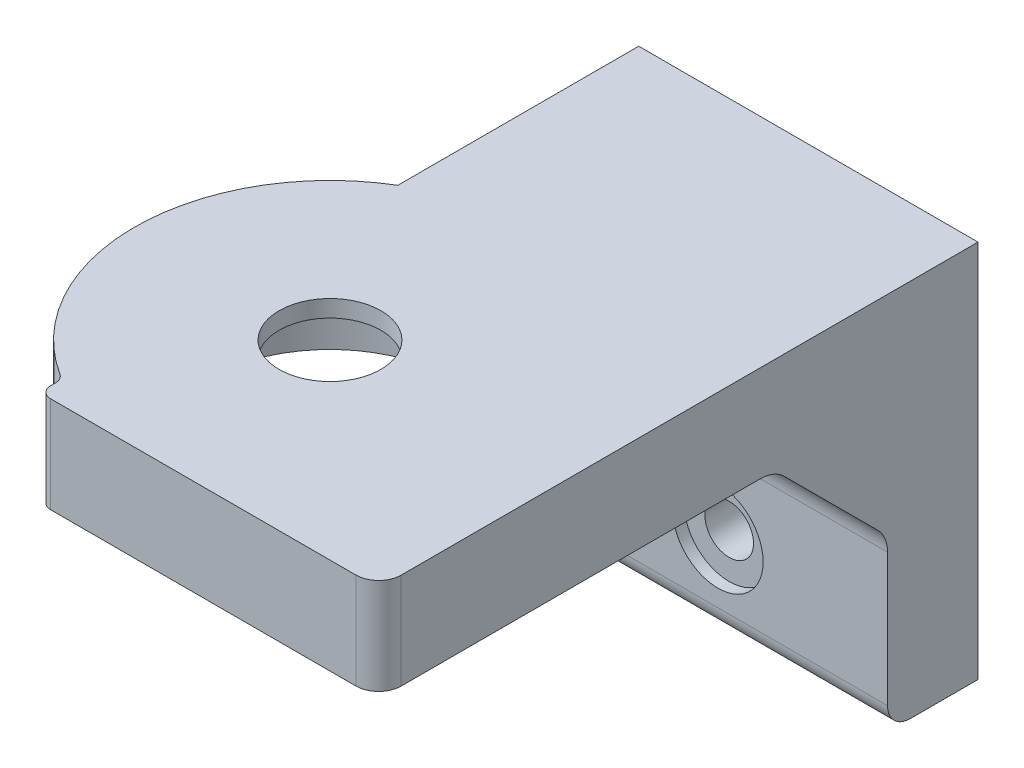
SolidWorks part; units mm, degrees
ref_plane "Front Plane" through (0, 0, 0) normal (0, 0, 1) x (1, 0, 0)
ref_plane "Top Plane" through (0, 0, 0) normal (0, 1, 0) x (1, 0, 0)
ref_plane "Right Plane" through (0, 0, 0) normal (1, 0, 0) x (0, 0, -1)
sketch "Croquis3" plane through (0, -625, 0) normal (0, 1, 0) x (1, 0, 0)
  line L0 (-40.3, 0) -> (-10.3, 0)
  line L1 (0, 0) -> (-20.6, 0) construction
  line L2 (-10.3, 0) -> (-10.3, -53)
  line L3 (-10.3, -270) -> (-10.3, 0) construction
  line L4 (-10.3, -53) -> (-40.3, -53)
  line L5 (-40.3, -53) -> (-40.3, -51)
  line L6 (-40.3, 0) -> (-40.3, -21.3)
  arc A0 (-40.3, -51) -> (-40.3, -21.3) centre (-31.45, -36.15) cw
  circle A1 centre (-31.45, -36.15) radius 11 construction
  circle A2 centre (-31.45, -36.15) radius 11
  circle A5 centre (-31.45, -36.15) radius 4.5
  circle A6 centre (-31.45, -36.15) radius 4.5
  dimension "D1" = 2
  dimension "D2" = 53
  dimension "D3" = 0.5
extrude "Saliente-Extruir2" add sketch "Croquis3" against normal blind 1.5 contours A0 L5 L4 L2 L0 L6 A2 | A2 A6 region at (-25.9749, -625, 25.0897) region at (-42.1389, -625, 36.15)
extrude "Saliente-Extruir3" add sketch "Croquis3<3>" against normal blind 7 from surface contours A0 L5 L4 L2 L0 L6 A2 region at (-25.9749, -625, 25.0897) starting at face at (-31.7062, -626.5, 29.7167)
sketch "Croquis3<3>" plane through (0, -625, 0) normal (0, 1, 0) x (1, 0, 0) same geometry as "Croquis3"
sketch "Croquis4" plane through (0, 0, 0) normal (0, 0, -1) x (-1, 0, 0)
  line L0 (10.3, -633.5) -> (10.3, -625) construction
  line L1 (40.3, -633.5) -> (10.3, -633.5)
  line L2 (40.3, -633.5) -> (40.3, -658.5)
  line L3 (40.3, -658.5) -> (10.3, -658.5)
  line L4 (10.3, -633.5) -> (10.3, -658.5)
  dimension "D1" = 25
extrude "Saliente-Extruir4" add sketch "Croquis4" against normal blind 8
chamfer "Chaflán1" distance 10 1 edges at (-25.3, -633.5, 8)
sketch "Croquis5" plane through (0, 0, 8) normal (0, 0, 1) x (1, 0, 0)
  line L0 (-40.3, -651) -> (-10.3, -651) construction
  line L1 (-40.3, -658.5) -> (-40.3, -643.5) construction
  line L2 (-10.3, -643.5) -> (-10.3, -658.5) construction
  circle A0 centre (-25.3, -651) radius 2.15
  circle A1 centre (-25.3, -651) radius 4
  dimension "D1" = 4.3
  dimension "D3" = 8
  dimension "D2" = 15
extrude "Cortar-Extruir1" cut sketch "Croquis5" against normal through all contours L0 A0 | A0 L0 region at (-25.3, -651.9125, 8) region at (-25.3, -650.0875, 8)
fillet "Redondeo1" radius 1 2 edges at (-40.3, -629.25, 51) (-40.3, -629.25, 53)
fillet "Redondeo2" radius 2 1 edges at (-10.3, -629.25, 53)
fillet "Redondeo3" radius 3 2 edges at (-25.3, -643.5, 8) (-25.3, -633.5, 18)
fillet "Redondeo4" radius 2 1 edges at (-25.3, -658.5, 8)
extrude "Cortar-Extruir2" cut sketch "Croquis5<3>" against normal blind 1 contours L0 A1 A0 | A1 L0 A0 region at (-25.3, -648.7606, 8) region at (-22.225, -651.0894, 8)
sketch "Croquis5<3>" plane through (0, 0, 8) normal (0, 0, 1) x (1, 0, 0) same geometry as "Croquis5"
